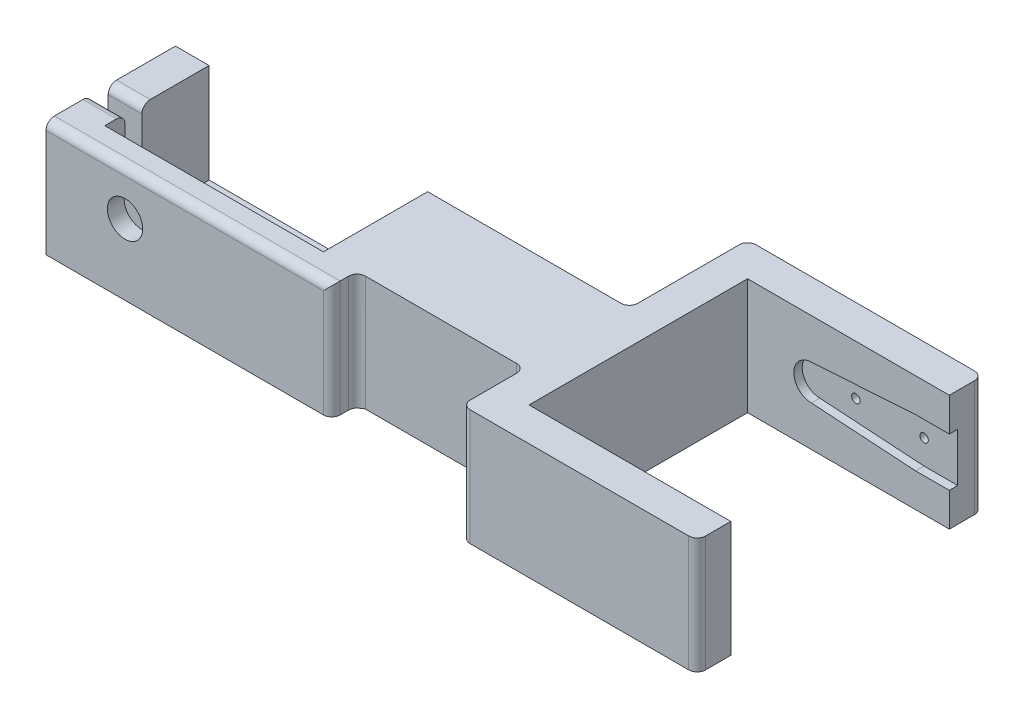
SolidWorks part; units mm, degrees
ref_plane "Front Plane" through (0, 0, 0) normal (0, 0, 1) x (1, 0, 0)
ref_plane "Top Plane" through (0, 0, 0) normal (0, 1, 0) x (1, 0, 0)
ref_plane "Right Plane" through (0, 0, 0) normal (1, 0, 0) x (0, 0, -1)
sketch "Sketch1" plane through (0, 0, 0) normal (0, 0, 1) x (1, 0, 0)
  line L1 (-37.5, -8.5) -> (37.5, -8.5) construction
  line L2 (-37.5, -8.5) -> (-37.5, 8.5) construction
  line L3 (-37.5, 8.5) -> (37.5, 8.5) construction
  line L4 (37.5, -8.5) -> (37.5, 8.5) construction
  line L5 (-37.5, -8.5) -> (37.5, 8.5) construction
  line L6 (-37.5, 8.5) -> (37.5, -8.5) construction
  line L7 (-42.5, 13.5) -> (-32.5, 13.5)
  line L8 (-42.5, 13.5) -> (-42.5, -16)
  line L9 (-42.5, -16) -> (-32.5, -16)
  line L10 (-32.5, 13.5) -> (-32.5, -16)
  line L11 (32.5, 13.5) -> (42.5, 13.5)
  line L12 (32.5, 13.5) -> (32.5, -16)
  line L13 (32.5, -16) -> (42.5, -16)
  line L14 (42.5, 13.5) -> (42.5, -16)
  line L15 (-42.5, -16) -> (42.5, -16)
  line L16 (-42.5, -16) -> (-42.5, -21)
  line L17 (-42.5, -21) -> (42.5, -21)
  line L18 (42.5, -16) -> (42.5, -21)
  line L19 (42.5, -21) -> (92.5, -21)
  line L20 (42.5, -21) -> (42.5, 13.5)
  line L21 (42.5, 13.5) -> (92.5, 13.5)
  line L22 (92.5, -21) -> (92.5, 13.5)
  circle A0 centre (-37.5, 8.5) radius 2.75
  circle A1 centre (37.5, 8.5) radius 2.75
  circle A2 centre (-37.5, -8.5) radius 2.75
  circle A3 centre (37.5, -8.5) radius 2.75
  point P0 (0, 0)
  point P19 (-37.5, 13.5)
  point P21 (37.5, 13.5)
  dimension "D1" = 5.5
  dimension "D2" = 17
  dimension "D3" = 75
  dimension "D4" = 10
  dimension "D5" = 5
  dimension "D6" = 7.5
  dimension "D7" = 5
  dimension "D8" = 50
extrude "Boss-Extrude1" add sketch "Sketch1" along normal mid plane 31 contours L10 L7 L8 L9 A2 A0 | L18 L13 L15 L9 L16 L17 | L14 L11 L12 L13 A3 A1 | A0 | A2 | A1 | A3 | L19 L22 L21 L14 L18 region at (-37.5, -1.49, 0) region at (0, -18.5, 0) region at (37.5, -1.49, 0) region at (67.5, -3.75, 0) region at (-37.5, 8.5, 0) region at (37.5, 8.5, 0) region at (-37.5, -8.5, 0) region at (37.5, -8.5, 0)
sketch "Sketch15" plane through (0, 0, -15.5) normal (0, 0, -1) x (-1, 0, 0)
  line L0 (42.5, -16) -> (-32.5, -16) construction
  line L1 (42.5, -16) -> (42.5, -21) construction
  line L2 (42.5, -21) -> (-42.5, -21) construction
  line L3 (-32.5, -16) -> (-42.5, -21) construction
  line L4 (-32.5, -16) -> (-42.5, -16)
  line L5 (-32.5, 13.5) -> (-32.5, -16)
  line L6 (-42.5, 13.5) -> (-32.5, 13.5)
  line L8 (-32.5, -16) -> (-42.5, -16)
  line L9 (-32.5, 13.5) -> (-32.5, -16)
  line L10 (-42.5, 13.5) -> (-32.5, 13.5)
  line L12 (32.5, -16) -> (42.5, -16)
  line L13 (32.5, 13.5) -> (32.5, -16)
  line L14 (42.5, 13.5) -> (32.5, 13.5)
  line L15 (42.5, -16) -> (42.5, 13.5)
  line L16 (32.5, -16) -> (42.5, -16)
  line L17 (32.5, 13.5) -> (32.5, -16)
  line L18 (42.5, 13.5) -> (32.5, 13.5)
  line L19 (42.5, -16) -> (42.5, 13.5)
  line L20 (42.5, -16) -> (-32.5, -16)
  line L21 (42.5, -16) -> (42.5, -21)
  line L22 (42.5, -21) -> (-42.5, -21)
  line L23 (-32.5, -16) -> (-42.5, -21)
  circle A1 centre (-37.5, -8.5) radius 2.75
  circle A2 centre (-37.5, -8.5) radius 2.75
  circle A3 centre (37.5, -8.5) radius 2.75
  circle A4 centre (37.5, -8.5) radius 2.75
  circle A5 centre (-37.5, 8.5) radius 2.75
  circle A6 centre (-37.5, 8.5) radius 2.75
  circle A7 centre (37.5, 8.5) radius 2.75
  circle A8 centre (37.5, 8.5) radius 2.75
  dimension "D1" = 0
  dimension "D2" = 0
  dimension "D3" = 0
  dimension "D4" = 0
  dimension "D5" = 0
  dimension "D6" = 0
extrude "Cut-Extrude5" cut sketch "Sketch15" against normal blind 10 contours A6 | A2 | A8 | A4 region at (37.5, -8.5, -15.5) region at (-37.5, -8.5, -15.5) region at (37.5, 8.5, -15.5) region at (-37.5, 8.5, -15.5)
sketch "Sketch2" plane through (0, 0, 15.5) normal (0, 0, 1) x (1, 0, 0)
  line L0 (32.5, 13.5) -> (32.5, -16) construction
  line L1 (-42.5, -21) -> (42.5, -21)
  line L2 (-42.5, -21) -> (-42.5, 13.5)
  line L3 (-42.5, 13.5) -> (42.5, 13.5)
  line L4 (42.5, -21) -> (42.5, 13.5)
  line L5 (32.5, 13.5) -> (92.5, 13.5) construction
  circle A0 centre (-19, 0) radius 1.6 construction
  circle A1 centre (-19, 0) radius 1.6 construction
  circle A2 centre (-19, 0) radius 5.25
  point P10 (0, 0)
  dimension "D1" = 10.5
  dimension "D2" = 10
extrude "Boss-Extrude2" add sketch "Sketch2" along normal blind 7.5
sketch "Sketch4" plane through (92.5, 0, 0) normal (1, 0, 0) x (0, 0, -1)
  line L5 (-23, -3.75) -> (8.15, -3.75) construction
  line L11 (-23, -21) -> (-23, 13.5) construction
  line L13 (-34.35, -21) -> (50.65, -21)
  line L14 (-34.35, -21) -> (-34.35, 13.5)
  line L15 (-34.35, 13.5) -> (50.65, 13.5)
  line L16 (50.65, -21) -> (50.65, 13.5)
  line L17 (-34.35, -21) -> (50.65, 13.5) construction
  line L18 (-34.35, 13.5) -> (50.65, -21) construction
  point P20 (8.15, -3.75)
  dimension "D1" = 85
  dimension "D3" = 31.15
  dimension "D4" = 34.5
extrude "Boss-Extrude3" add sketch "Sketch4" along normal blind 10
sketch "Sketch5" plane through (102.5, 0, 0) normal (1, 0, 0) x (0, 0, -1)
  line L1 (-34.35, 13.5) -> (-24.35, 13.5)
  line L2 (-34.35, 13.5) -> (-34.35, -21)
  line L3 (-34.35, -21) -> (-24.35, -21)
  line L4 (-24.35, 13.5) -> (-24.35, -21)
  line L5 (50.65, -21) -> (50.65, 13.5) construction
  line L6 (50.65, 13.5) -> (40.65, 13.5)
  line L7 (50.65, 13.5) -> (50.65, -21)
  line L8 (50.65, -21) -> (40.65, -21)
  line L9 (40.65, 13.5) -> (40.65, -21)
  line L11 (50.65, 13.5) -> (-34.35, 13.5) construction
  line L13 (-34.35, 13.5) -> (-34.35, -21) construction
  line L14 (-34.35, -21) -> (50.65, -21) construction
  dimension "D1" = 10
extrude "Boss-Extrude4" add sketch "Sketch5" along normal blind 60
sketch "Sketch6" plane through (0, 0, 24.35) normal (0, 0, -1) x (-1, 0, 0)
  line L0 (-162.5, -3.75) -> (-152.5, -3.75) construction
  line L1 (-162.5, -21) -> (-162.5, 13.5) construction
  circle A0 centre (-152.5, -3.75) radius 5
  dimension "D1" = 10
  dimension "D2" = 10
extrude "Boss-Extrude5" add sketch "Sketch6" along normal blind 5
sketch "Sketch8" plane through (0, 0, -40.65) normal (0, 0, 1) x (1, 0, 0)
  line L1 (121.5, 1.5) -> (152.5, 3.5)
  line L6 (152.5, -11) -> (162.5, -11)
  line L7 (121.5, -9) -> (152.5, -11)
  line L8 (162.5, 13.5) -> (162.5, -21) construction
  line L9 (152.5, 3.5) -> (162.5, 3.5)
  line L10 (162.5, 3.5) -> (162.5, -11)
  circle A0 centre (152.5, -3.75) radius 5.65 construction
  circle A1 centre (152.5, -3.75) radius 5.65 construction
  circle A6 centre (121.5, -3.75) radius 5.25
  circle A11 centre (152.5, -3.75) radius 7.25
  line M9 (162.5, -21) -> (162.5, 13.5)
  dimension "D5" = 14.5
  dimension "D1" = 10.5
  dimension "D8" = 31
extrude "Cut-Extrude2" cut sketch "Sketch8" against normal blind 2.5 contours A1 | A11 L6 L9 M9 | L1 A11 L7 | A11 L1 A6 L7 | A6 region at (136.5013, -3.75, -40.65) region at (121.5, -3.75, -40.65) region at (152.5001, -3.75, -40.65) region at (160.043, -3.75, -40.65)
sketch "Sketch10" plane through (-42.5, 0, 0) normal (-1, 0, 0) x (0, 0, 1)
  line L0 (23, -21) -> (23, 13.5) construction
  line L1 (4.5, 13.5) -> (9.5, 13.5)
  line L2 (4.5, 13.5) -> (4.5, -5)
  line L3 (4.5, -5) -> (9.5, -5)
  line L4 (9.5, 13.5) -> (9.5, -5)
  line L5 (23, -21) -> (-15.5, -21) construction
  line L6 (23, 13.5) -> (-15.5, 13.5) construction
  dimension "D2" = 5
  dimension "D3" = 13.5
  dimension "D4" = 16
extrude "Cut-Extrude4" cut sketch "Sketch10" against normal up to surface (10 mm away) up to face at (-32.5, -1.25, 0)
sketch "Sketch11" plane through (0, 0, -40.65) normal (0, 0, -1) x (-1, 0, 0)
  circle A0 centre (-132.2, -3.75) radius 4.856
  circle A1 centre (-152.5, -3.75) radius 5
  circle A2 centre (-152.5, -3.75) radius 5
  dimension "D2" = 20.3
  dimension "D1" = 0
sketch "Sketch12" plane through (0, 0, -50.65) normal (0, 0, -1) x (-1, 0, 0)
  point P0 (-132.2, -3.75)
  point P3 (-152.5, -3.75)
hole_wizard "Ø2.5mm Dowel Hole1" positions "Sketch12" profile "Sketch13" hole size "Ø2.5" standard "ANSI Metric"
sketch "Sketch13" plane through (132.2, -3.75, -50.65) normal (1, 0, 0) x (0, 1, 0)
  line L0 (0, 0) -> (0, 10.7511)
  line L1 (0, 10.7511) -> (1.25, 10)
  line L2 (1.25, 10) -> (1.25, 0)
  line L5 (1.25, 0) -> (0, 0)
  line L10 (0, 10.7511) -> (-1.25, 10) construction
  line L11 (0, -6.35) -> (0, 107.95) construction
  dimension "Hole Dia." = 2.5
  dimension "Hole Depth" = 10
  dimension "Drill Angle" = 118
fillet "Fillet1" radius 2.5 9 edges at (92.5, -3.75, -15.5) (0, 13.5, 23) (92.5, -3.75, 34.35) (162.5, -3.75, 34.35) (162.5, -3.75, -50.65) (92.5, -3.75, -50.65) (92.5, -3.75, 15.5) (42.5, -3.75, 15.5) (42.5, -3.75, 23)
sketch "Sketch14" plane through (0, 0, 15.5) normal (0, 0, -1) x (-1, 0, 0)
  circle A0 centre (19, 0) radius 5.25 construction
  circle A1 centre (19, 0) radius 5.25
extrude "Boss-Extrude6" add sketch "Sketch14" against normal blind 2.5
fillet "Fillet2" radius 2.5 4 edges at (-37.5, -5, 9.5) (-37.5, -5, 4.5) (-37.5, 13.5, 9.5) (-37.5, 13.5, 4.5)
sketch "Sketch17" plane through (0, -21, 0) normal (0, -1, 0) x (1, 0, 0)
  line L0 (-32.5, 9.5) -> (-42.5, 9.5) construction
  line L1 (-42.5, 4.5) -> (-32.5, 4.5) construction
  line L2 (-32.5, 9.5) -> (-42.5, 9.5) construction
  line L3 (-42.5, 4.5) -> (-32.5, 4.5) construction
  line L4 (-42.5, 23) -> (-42.5, -15.5) construction
  line L5 (-42.5, 13.25) -> (102.5, 13.25)
  line L6 (-42.5, 13.25) -> (-42.5, 0.75)
  line L7 (-42.5, 0.75) -> (102.5, 0.75)
  line L8 (102.5, 13.25) -> (102.5, 0.75)
  line L9 (102.5, 24.35) -> (102.5, -40.65) construction
  line L10 (-32.5, 9.5) -> (-32.5, 4.5) construction
  point P12 (-32.5, 7)
  point P13 (102.5, 7)
  dimension "D1" = 12.5
extrude "Cut-Extrude7" cut sketch "Sketch17" against normal blind 2.5
chamfer "Chamfer1" distance 2.5 angle 45 2 edges at (30, -21, 0.75) (30, -21, 13.25)
